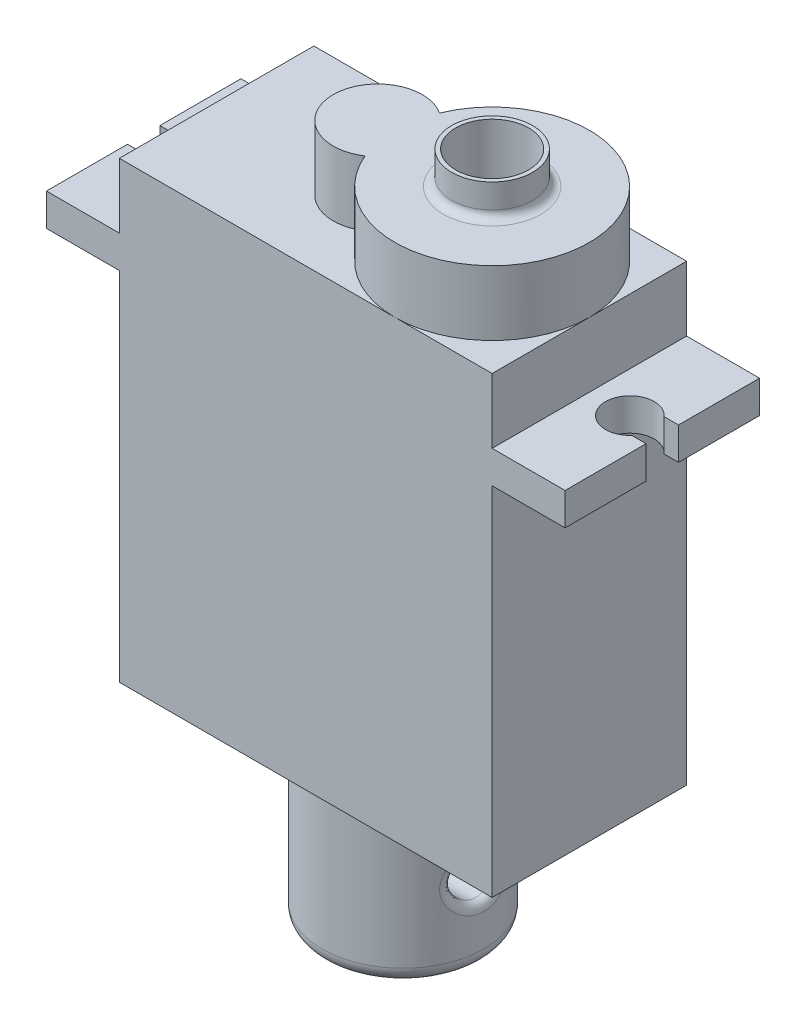
SolidWorks part; units mm, degrees
ref_plane "Front Plane" through (0, 0, 0) normal (0, 0, 1) x (1, 0, 0)
ref_plane "Top Plane" through (0, 0, 0) normal (0, 1, 0) x (1, 0, 0)
ref_plane "Right Plane" through (0, 0, 0) normal (1, 0, 0) x (0, 0, -1)
sketch "Sketch1" plane through (0, 0, 0) normal (0, 1, 0) x (1, 0, 0)
  line L1 (-11.5, 6) -> (11.5, 6)
  line L2 (-11.5, 6) -> (-11.5, -6)
  line L3 (-11.5, -6) -> (11.5, -6)
  line L4 (11.5, 6) -> (11.5, -6)
  line L5 (-11.5, 6) -> (11.5, -6) construction
  line L6 (-11.5, -6) -> (11.5, 6) construction
  point P0 (0, 0)
  dimension "D1" = 12
  dimension "D2" = 23
extrude "Boss-Extrude1" add sketch "Sketch1" along normal blind 22
sketch "Sketch2" plane through (0, 22, 0) normal (0, 1, 0) x (1, 0, 0)
  line L0 (11.5, 6) -> (-11.5, 6) construction
  line L1 (-16, 6) -> (16, 6)
  line L2 (-16, 6) -> (-16, -6)
  line L3 (-16, -6) -> (16, -6)
  line L4 (16, 6) -> (16, -6)
  line L5 (-16, 6) -> (16, -6) construction
  line L6 (-16, -6) -> (16, 6) construction
  point P1 (0, 0)
  dimension "D1" = 0
  dimension "D2" = 16
extrude "Boss-Extrude2" add sketch "Sketch2" along normal blind 2
sketch "Sketch3" plane through (0, 24, 0) normal (0, 1, 0) x (1, 0, 0)
  line L0 (-16, -6) -> (16, -6) construction
  line L1 (-11.5, 6) -> (11.5, 6)
  line L2 (-11.5, 6) -> (-11.5, -6)
  line L3 (-11.5, -6) -> (11.5, -6)
  line L4 (11.5, 6) -> (11.5, -6)
  line L5 (-11.5, 6) -> (11.5, -6) construction
  line L6 (-11.5, -6) -> (11.5, 6) construction
  point P0 (0, 0)
  dimension "D1" = 23
sketch "Sketch4" plane through (0, 24, 0) normal (0, 1, 0) x (1, 0, 0)
  line L0 (-16.6395, 1) -> (-15.118, 1)
  line L1 (-16.6395, -1) -> (-15.118, -1)
  line L2 (-16.6395, 1) -> (-16.6395, -1)
  line L3 (15.118, 1) -> (17.1213, 1)
  line L4 (17.1213, 1) -> (17.1213, -1)
  line L5 (17.1213, -1) -> (15.118, -1)
  arc A0 (-15.118, -1) -> (-15.118, 1) centre (-14, 0) ccw
  arc A1 (15.118, 1) -> (15.118, -1) centre (14, 0) ccw
  dimension "D3" = 3
  dimension "D4" = 3
  dimension "D1" = 28
  dimension "D2" = 14
  dimension "D5" = 1
  dimension "D6" = 1
extrude "Cut-Extrude1" cut sketch "Sketch4" against normal blind 5
extrude "Boss-Extrude4" add sketch "Sketch3" along normal blind 4
sketch "Sketch5" plane through (0, 28, 0) normal (0, 1, 0) x (1, 0, 0)
  line L1 (11.5, -6) -> (11.5, 6) construction
  line L2 (11.5, 6) -> (-11.5, 6) construction
  line L3 (-11.5, -6) -> (11.5, -6) construction
  arc A0 (-0.0432, -2.2962) -> (-0.0432, 2.2962) centre (5.5, 0) ccw
  arc A2 (-0.0432, 2.2962) -> (-0.0432, -2.2962) centre (-1.5565, 0) ccw
  dimension "D1" = 5.5
extrude "Boss-Extrude5" add sketch "Sketch5" along normal blind 4
sketch "Sketch6" plane through (0, 32, 0) normal (0, 1, 0) x (1, 0, 0)
  circle A0 centre (5.5, 0) radius 2.25
  arc A1 (-0.0432, -2.2962) -> (-0.0432, 2.2962) centre (5.5, 0) ccw construction
  circle A2 centre (5.5, 0) radius 2.5
  dimension "D2" = 4.5
  dimension "D3" = 5
  dimension "D1" = 0
extrude "Boss-Extrude6" add sketch "Sketch6" along normal blind 2
sketch "Sketch7" plane through (0, 32, 0) normal (0, 1, 0) x (1, 0, 0)
  circle A0 centre (5.5, 0) radius 2.25
extrude "Cut-Extrude2" cut sketch "Sketch7" against normal blind 4
sketch "Sketch8" plane through (0, 0, 0) normal (0, -1, 0) x (1, 0, 0)
  circle A0 centre (0, 0) radius 5
  dimension "D1" = 10
extrude "Boss-Extrude7" add sketch "Sketch8" along normal blind 10
sketch "Sketch9" plane through (11.5, 0, 0) normal (1, 0, 0) x (0, 0, -1)
  line L0 (-5, 0) -> (5, 0) construction
  circle A0 centre (0, -5) radius 1.5
  dimension "D2" = 3
  dimension "D1" = 5
extrude "Cut-Extrude3" cut sketch "Sketch9" against normal blind 20
fillet "Fillet1" radius 1 1 edges at (0, -10, -5)
fillet "Fillet2" radius 1 1 edges at (0, 0, -5)
fillet "Fillet3" radius 0.5 2 edges at (-4.7775, -5.2723, 1.4751) (4.7775, -4.7277, 1.4751)
fillet "Fillet4" radius 0.5 1 edges at (5.5, 32, 2.5)
